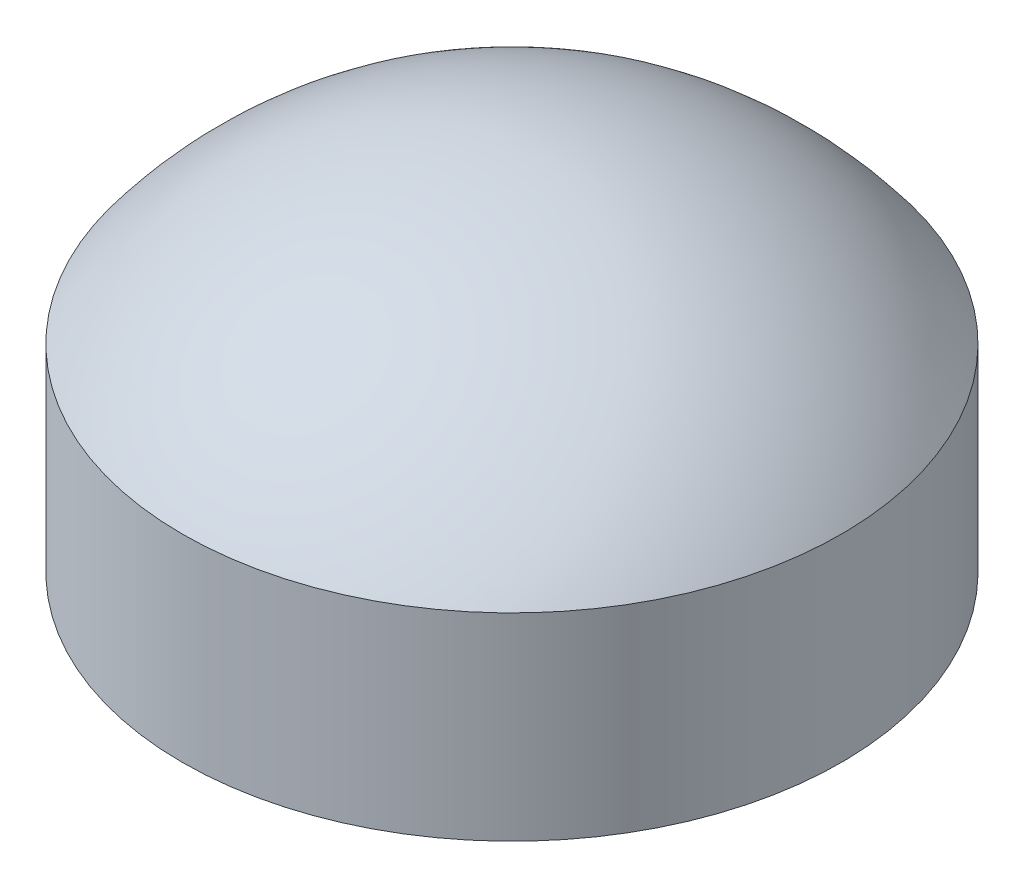
SolidWorks part; units mm, degrees
ref_plane "Front Plane" through (0, 0, 0) normal (0, 0, 1) x (1, 0, 0)
ref_plane "Top Plane" through (0, 0, 0) normal (0, 1, 0) x (1, 0, 0)
ref_plane "Right Plane" through (0, 0, 0) normal (1, 0, 0) x (0, 0, -1)
sketch "Sketch1" plane through (0, 0, 0) normal (0, 1, 0) x (1, 0, 0)
  circle A0 centre (0, 0) radius 20
  dimension "D1" = 40
extrude "Boss-Extrude1" add sketch "Sketch1" along normal blind 12
dome "Dome1" faces to dome 1 distance 10 reverse direction no elliptical dome no face at (0, 12, 20) parameters "D1"=10
